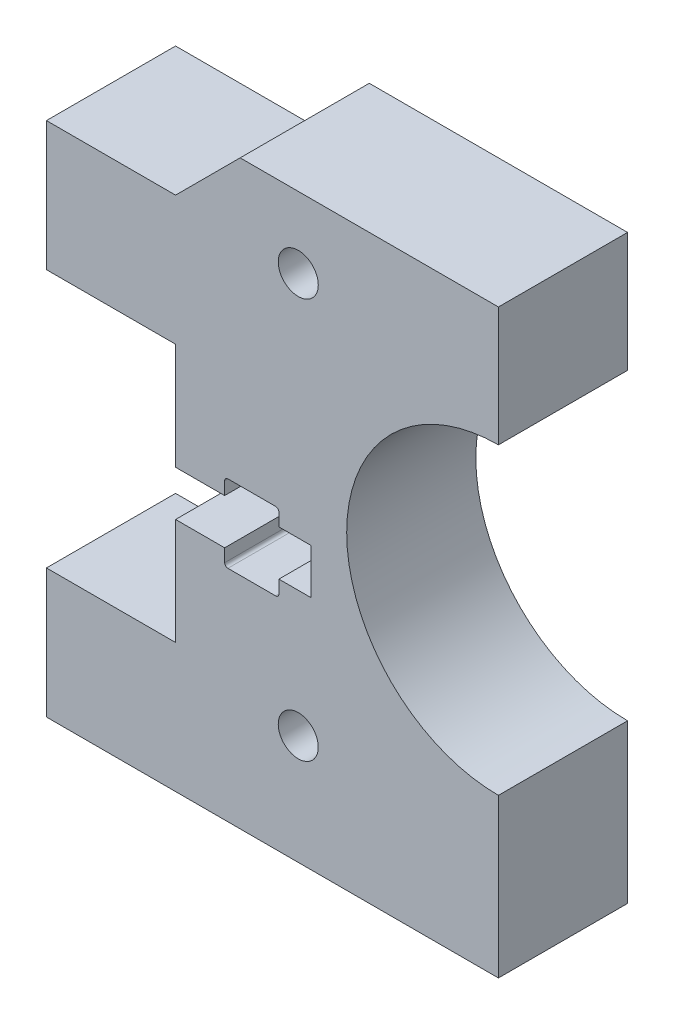
SolidWorks part; units mm, degrees
ref_plane "Front Plane" through (0, 0, 0) normal (0, 0, 1) x (1, 0, 0)
ref_plane "Top Plane" through (0, 0, 0) normal (0, 1, 0) x (1, 0, 0)
ref_plane "Right Plane" through (0, 0, 0) normal (1, 0, 0) x (0, 0, -1)
sketch "Sketch1" plane through (0, 0, 0) normal (0, 0, 1) x (1, 0, 0)
  line L0 (0, 0) -> (0, -50) construction
  line L1 (-10, -40) -> (0, -40) construction
  line L2 (25, -50) -> (25, 0) construction
  line L3 (25, 0) -> (0, 0) construction
  line L4 (0, 0) -> (0, -5)
  line L5 (0, -5) -> (-10, -5)
  line L6 (-10, -5) -> (-10, -15)
  line L7 (-10, -15) -> (0, -15)
  line L8 (0, -15) -> (0, -35)
  line L9 (25, -50) -> (0, -50) construction
  line L10 (0, -50) -> (25, -50)
  line L11 (-10, -35) -> (0, -35)
  line L12 (-10, -45) -> (-10, -35)
  line L13 (0, -45) -> (-10, -45)
  line L14 (25, -50) -> (25, 0)
  line L15 (0, 0) -> (25, 0)
  line L16 (0, -50) -> (0, -45)
  line L17 (-10, -10) -> (0, -10) construction
  line L18 (0, -25) -> (25, -25) construction
  dimension "D1" = 10
  dimension "D6" = 25
  dimension "D2" = 25
extrude "Boss-Extrude1" add sketch "Sketch1" along normal blind 10
sketch "Sketch2" plane through (0, 0, 10) normal (0, 0, 1) x (1, 0, 0)
  line L0 (25, -21) -> (0, -21) construction
  line L1 (25, -50) -> (25, 0) construction
  line L2 (0, -15) -> (0, -35) construction
  line L3 (25, -21) -> (9.5, -5.5) construction
  line L4 (25, -21) -> (9.5, -36.5) construction
  circle A0 centre (25, -21) radius 11.75
  circle A1 centre (9.5, -5.5) radius 1.55
  circle A2 centre (9.5, -36.5) radius 1.55
  point P6 (0, -25)
  dimension "D2" = 23.5
  dimension "D5" = 3.1
  dimension "D1" = 4
  dimension "D3" = 45
  dimension "D4" = 15.5
extrude "motor" cut sketch "Sketch2" against normal through all
sketch "Sketch3" plane through (0, 0, 10) normal (0, 0, 1) x (1, 0, 0)
  line L0 (0, -25) -> (10.5, -25) construction
  line L1 (0, -15) -> (0, -35) construction
  line L2 (10.5, -26.75) -> (10.5, -23.25) construction
  line L3 (10.5, -23.25) -> (0, -23.25) construction
  line L4 (0, -26.75) -> (0, -23.25)
  line L5 (0, -23.25) -> (3.8, -23.25)
  line L6 (3.8, -23.25) -> (3.8, -22.25)
  line L7 (4.05, -22) -> (7.75, -22)
  line L8 (8, -22.25) -> (8, -23.25)
  line L9 (8, -23.25) -> (10.5, -23.25)
  line L10 (10.5, -23.25) -> (10.5, -26.75)
  line L11 (10.5, -26.75) -> (0, -26.75) construction
  line L12 (8, -26.75) -> (10.5, -26.75)
  line L13 (8, -27.75) -> (8, -26.75)
  line L14 (4.05, -28) -> (7.75, -28)
  line L15 (3.8, -26.75) -> (3.8, -27.75)
  line L16 (0, -26.75) -> (3.8, -26.75)
  arc A0 (4.05, -28) -> (3.8, -27.75) centre (4.05, -27.75) cw
  arc A1 (8, -27.75) -> (7.75, -28) centre (7.75, -27.75) cw
  arc A2 (7.75, -22) -> (8, -22.25) centre (7.75, -22.25) cw
  arc A3 (3.8, -22.25) -> (4.05, -22) centre (4.05, -22.25) cw
  point P18 (3.8, -28)
  point P21 (8, -28)
  point P24 (8, -22)
  point P27 (3.8, -22)
  dimension "D6" = 0.25
  dimension "D1" = 1.75
  dimension "D2" = 8
  dimension "D3" = 10.5
  dimension "D4" = 3
  dimension "D5" = 4.2
extrude "screw" cut sketch "Sketch3" against normal through all
sketch "Sketch4" plane through (0, 0, 10) normal (0, 0, 1) x (1, 0, 0)
  line L0 (0, -45) -> (25, -45)
  line L1 (25, -50) -> (25, -32.75) construction
  line L2 (25, -45) -> (25, -50)
  line L3 (25, -50) -> (0, -50)
  line L4 (0, -50) -> (0, -45)
  line L5 (0, -5) -> (5, 0)
  line L6 (25, 0) -> (0, 0) construction
  line L7 (5, 0) -> (0, 0)
  line L8 (0, 0) -> (0, -5)
  dimension "D1" = 45
extrude "Cut-Extrude3" cut sketch "Sketch4" against normal through all
equation "\"X-ROD-SPACING\"=45"
equation "\"Y-ROD-SPACING\"=75"
equation "\"Z-ROD-SPACING\"=17.5"
equation "\"Y-BED-OFFSET\"=2"
equation "\"Y-BED-ROD-INSET\"=3.5"
equation "\"T-SLOT-NUT-FILLET-RADIUS\"=0.25"
equation "\"T-SLOT-SCREW-SHAFT-RADIUS\"=1.75"
equation "\"T-SLOT-SCREW-SHAFT-CUTOUT-LENGTH\"=10.5"
equation "\"T-SLOT-NUT-DEPTH\"=4.2"
equation "\"T-SLOT-NUT-WIDTH\"=3"
equation "\"T-SLOT-NUT-END-DISTANCE\"=8"
equation "\"ACRYLIC-THICKNESS\"=10"
equation "\"ACRYLIC-THICKNESS2\"=4.5"
equation "\"ACRYLIC-TAB-CUTOUT-SIZE\"=\"ACRYLIC-THICKNESS\"+\"ACRYLIC-TAB-TOLERANCE\"*2"
equation "\"ACRYLIC-TAB-WIDTH\"=\"ACRYLIC-THICKNESS\""
equation "\"ACRYLIC-M3-HOLE\"=3.1"
equation "\"SMOOTHROD-CAP-SCREW-DISTANCE\"=20"
equation "\"FRAME-WIDTH-INNER\"=370"
equation "\"NEMA17-HOLE-SPACING\"=31"
equation "\"NEMA17-CENTRAL-CUTOUT\"=22.5"
equation "\"Z-BRACKET-REACH\"=55"
equation "\"TOP-BRACKET-SPACING\"=40"
equation "\"SMOOTHROD-X-LENGTH\"=350"
equation "\"SMOOTHROD-Y-LENGTH\"=350"
equation "\"SMOOTHROD-Z-LENGTH\"=350"
equation "\"SMOOTHROD-TIGHTENING-HEADROOM\"=.25"
equation "\"LEADSCREW-Z-LENGTH\"=300"
equation "\"SCREW-LENGTH-FRAME\"=\"ACRYLIC-THICKNESS\" + 10"
equation "\"SCREW-HEAD-RADIUS\"=6"
equation "\"PRINTED-X-SMOOTHROD-DIAMETER\"=8.2"
equation "\"PRINTED-X-SMOOTHROD-CUTOUT\"=10"
equation "\"PRINTED-X-BASE-HEIGHT\"=10"
equation "\"PRINTED-LM8UU-CUTOUT-SIZE\"=15.25"
equation "\"PRINTED-LM8UU-CUTOUT-LENGTH\"=24.5"
equation "\"PRINTED-X-IDLER-HEIGHT\"=16"
equation "\"PSU-MOUNTING-WIDTH\"=95"
equation "\"PSU-MOUNTING-HEIGHT\"=177"
equation "\"D1@Sketch1\"=10"
equation "\"D3@Sketch1\"=10"
equation "\"D1@Boss-Extrude1\"=\"ACRYLIC-THICKNESS\""
equation "\"D2@Sketch2\"=\"NEMA17-CENTRAL-CUTOUT\"+1"
equation "\"D4@Sketch2\"=\"NEMA17-HOLE-SPACING\"/2"
equation "\"D5@Sketch2\"=\"ACRYLIC-M3-HOLE\""
equation "\"D1@Sketch3\"=\"T-SLOT-SCREW-SHAFT-RADIUS\""
equation "\"D3@Sketch3\"=\"T-SLOT-SCREW-SHAFT-CUTOUT-LENGTH\""
equation "\"D4@Sketch3\"=\"T-SLOT-NUT-WIDTH\""
equation "\"D2@Sketch3\"=\"T-SLOT-NUT-END-DISTANCE\""
equation "\"D5@Sketch3\"=\"T-SLOT-NUT-DEPTH\""
equation "\"D6@Sketch3\"=\"T-SLOT-NUT-FILLET-RADIUS\""
